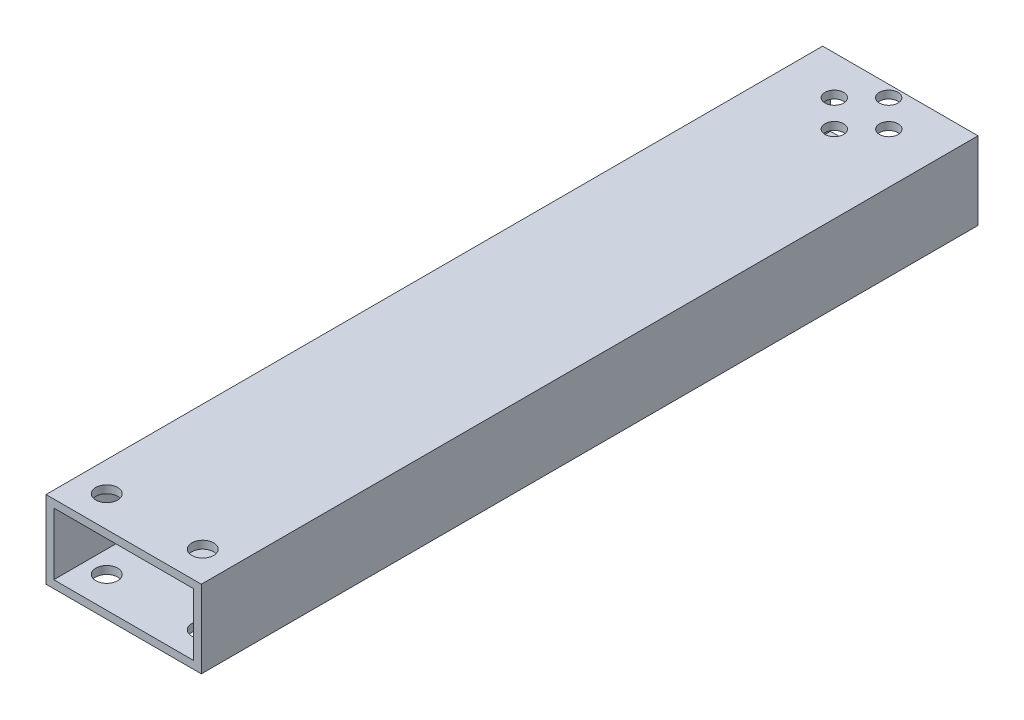
SolidWorks part; units mm, degrees
material "6061 Alloy"
ref_plane "Front Plane" through (0, 0, 0) normal (0, 0, 1) x (1, 0, 0)
ref_plane "Top Plane" through (0, 0, 0) normal (0, 1, 0) x (1, 0, 0)
ref_plane "Right Plane" through (0, 0, 0) normal (1, 0, 0) x (0, 0, -1)
sketch "Sketch1" plane through (0, 0, 0) normal (0, 0, 1) x (1, 0, 0)
  line L1 (-12.7, 6.35) -> (12.7, 6.35)
  line L2 (-12.7, 6.35) -> (-12.7, -6.35)
  line L3 (-12.7, -6.35) -> (12.7, -6.35)
  line L4 (12.7, 6.35) -> (12.7, -6.35)
  point P4 (-12.7, 0)
  point P6 (0, 6.35)
  dimension "D1" = 12.7
  dimension "D2" = 25.4
extrude "Boss-Extrude1" add sketch "Sketch1" along normal blind 127
sketch "Sketch4" plane through (0, 0, 0) normal (0, 0, -1) x (-1, 0, 0)
  line L0 (-12.7, -6.35) -> (-12.7, 6.35) construction
  line L1 (-11.43, 5.08) -> (11.43, 5.08)
  line L2 (-11.43, 5.08) -> (-11.43, -5.08)
  line L3 (-11.43, -5.08) -> (11.43, -5.08)
  line L4 (11.43, 5.08) -> (11.43, -5.08)
  line L5 (-12.7, 6.35) -> (12.7, 6.35) construction
  line L6 (12.7, -6.35) -> (-12.7, -6.35) construction
  line L7 (12.7, 6.35) -> (12.7, -6.35) construction
  dimension "D1" = 1.27
  dimension "D2" = 1.27
  dimension "D3" = 1.27
  dimension "D4" = 1.27
extrude "Cut-Extrude1" cut sketch "Sketch4" against normal through all
sketch "Sketch5" plane through (0, 6.35, 0) normal (0, 1, 0) x (1, 0, 0)
  line L0 (-12.7, -127) -> (-12.7, 0) construction
  line L1 (12.7, -127) -> (12.7, 0) construction
  line L2 (12.7, -127) -> (-12.7, -127) construction
  circle A0 centre (-7.8486, -121.92) radius 1.7907
  circle A1 centre (7.8486, -121.92) radius 1.7907
  dimension "D1" = 3.5814
  dimension "D2" = 3.5814
  dimension "D3" = 4.8514
  dimension "D4" = 4.8514
  dimension "D5" = 5.08
  dimension "D6" = 5.08
extrude "Cut-Extrude2" cut sketch "Sketch5" against normal through all both and the other way through all
sketch "Sketch6" plane through (0, -6.35, 0) normal (0, -1, 0) x (-1, 0, 0)
  line L0 (12.7, 0) -> (-12.7, 0) construction
  line L1 (12.7, -127) -> (12.7, 0) construction
  circle A0 centre (4.445, -6.35) radius 1.524
  circle A1 centre (-4.4704, -6.35) radius 1.524
  circle A2 centre (0, -6.35) radius 4.445 construction
  circle A3 centre (0, -1.905) radius 1.524
  circle A4 centre (0, -10.795) radius 1.524
  dimension "D1" = 3.048
  dimension "D2" = 3.048
  dimension "D6" = 8.89
  dimension "D7" = 3.048
  dimension "D8" = 3.048
  dimension "D3" = 8.9154
  dimension "D4" = 6.35
  dimension "D5" = 8.255
extrude "Cut-Extrude3" cut sketch "Sketch6" against normal through all both contours A3 | A1 | A4 | A0
